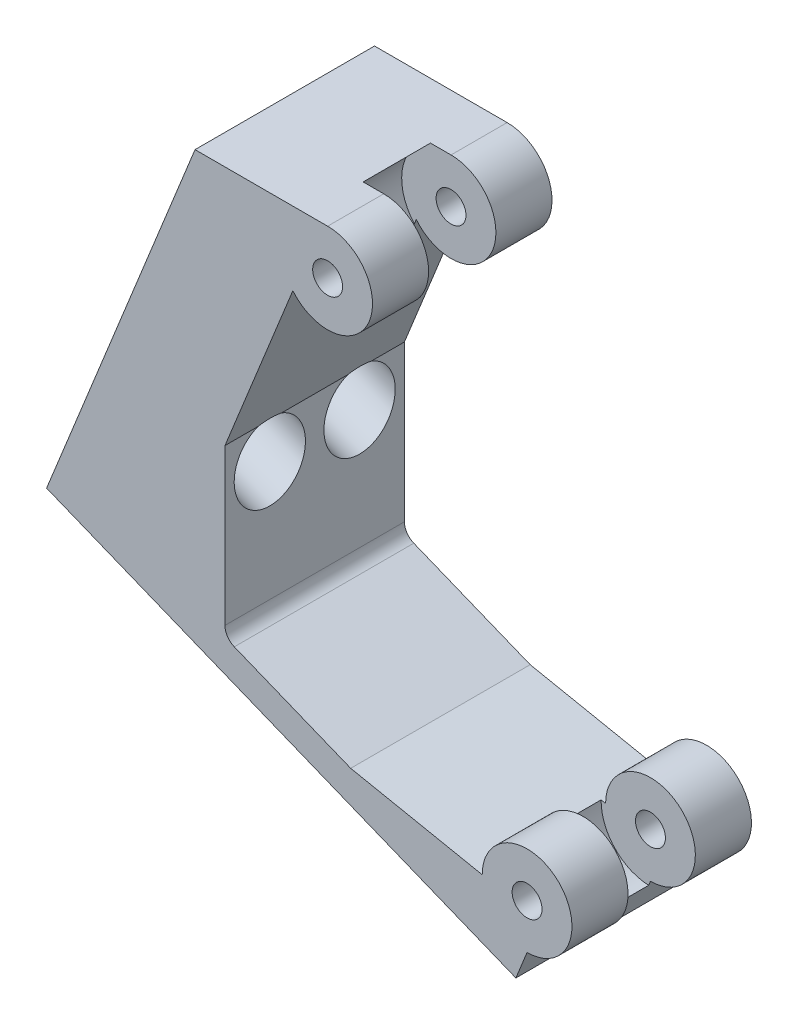
SolidWorks part; units mm, degrees
other "Markup1"
sketch "Sketch3" plane through (0, 0, 12) normal (0, 0, 1) x (1, 0, 0)
other "DetailItem1"
other "DetailItem3"
other "DetailItem5"
ref_plane "Front Plane" through (0, 0, 0) normal (0, 0, 1) x (1, 0, 0)
ref_plane "Top Plane" through (0, 0, 0) normal (0, 1, 0) x (1, 0, 0)
ref_plane "Right Plane" through (0, 0, 0) normal (1, 0, 0) x (0, 0, -1)
sketch "Sketch1" plane through (0, 0, 0) normal (0, 0, 1) x (1, 0, 0)
  line L2 (0, 6.6407) -> (0, 35.2105)
  line L3 (0, 35.2105) -> (8.8654, 35.2105)
  line L5 (6.5411, 30.3139) -> (2, 19.0743)
  line L6 (2, 19.0743) -> (2, 7.9897)
  line L7 (10.4069, 4.5931) -> (19.1992, 2.8287)
  line L11 (8.8654, 32.2105) -> (22.1992, 2.8287) construction
  line L15 (8.8654, 32.2105) -> (8.8654, 4.9405) construction
  line L16 (8.8654, 4.9405) -> (22.1992, 2.8287) construction
  line L17 (8.8654, 4.9405) -> (8.8654, -11.9834) construction
  line L21 (2, 7.9897) -> (10.4069, 4.5931)
  line L22 (-988.4786, -0.1713) -> (16.8603, -0.1713) construction
  line L23 (0, 6.6407) -> (21.45, -2.0257)
  line L24 (-905.7338, 372.5809) -> (46380.6427, -18732.3554) construction
  line L25 (22.1992, -0.1713) -> (50022.1992, -0.1713) construction
  line L26 (22.1992, -0.1713) -> (21.45, -2.0257)
  line L27 (-904.9846, 374.4353) -> (46381.392, -18730.501) construction
  line L28 (0.4221, 6.4701) -> (-46358.7706, 18736.7998) construction
  line L29 (2, 19.0743) -> (18732.3297, 46378.267) construction
  arc A0 (22.1992, -0.1713) -> (19.1992, 2.8287) centre (22.1992, 2.8287) ccw
  arc A1 (8.8654, 35.2105) -> (6.5411, 30.3139) centre (8.8654, 32.2105) cw
  circle A2 centre (8.8654, 32.2105) radius 1
  circle A3 centre (22.1992, 2.8287) radius 1
  dimension "D1" = 2
  dimension "D3" = 3
  dimension "D4" = 27.27
  dimension "D5" = 13.5
  dimension "D8" = 81
  dimension "D12" = 22
  dimension "D2" = 2
  dimension "D9" = 90
  dimension "D13" = 2
extrude "Boss-Extrude1" add sketch "Sketch1" along normal blind 12
ref_plane "midplane" through (0, 0, 6) normal (0, 0, 1) x (1, 0, 0)
sketch "Sketch2" plane through (0, 0, 6) normal (0, 0, 1) x (1, 0, 0)
  circle A0 centre (8.8654, 32.2105) radius 3.3
  circle A1 centre (22.1992, 2.8287) radius 3.3
  dimension "D1" = 6.6
extrude "Cut-Extrude1" cut sketch "Sketch2" against normal blind 2.25 and the other way blind 2.25
fillet "Fillet3" radius 1 1 edges at (2, 7.9897, 6)
ref_plane "Plane1" through (2.3065, 5.7088, 0) normal (-0.3746, -0.9272, 0) x (-0.9272, 0.3746, 0)
ref_plane "Plane2" through (-12.2296, 4.9411, 0) normal (-0.9272, 0.3746, 0) x (0, 0, -1)
sketch "Sketch4" plane through (-12.2296, 4.9411, 0) normal (-0.9272, 0.3746, 0) x (0, 0, -1)
  line L0 (6.6, -6.1571) -> (-6.6, -6.1571) construction
  line L1 (-12, -32.6466) -> (0, -32.6466)
  line L2 (-12, -32.6466) -> (-12, -6.1571)
  line L3 (-12, -6.1571) -> (0, -6.1571)
  line L4 (0, -32.6466) -> (0, -6.1571)
extrude "Boss-Extrude2" add sketch "Sketch4" against normal up to surface up to face at (0, 20.9256, 6)
sketch "Hole sketch" plane through (7.6836, 33.1417, 0) normal (-0.9272, 0.3746, 0) x (0, 0, -1)
  line L0 (-12, 17.4202) -> (0, 17.4202) construction
  line L1 (-8.25, 3.3877) -> (-3.75, 3.3877) construction
  line L2 (0, 24.8243) -> (0, 15.1722) construction
  line L3 (-6, -1.7766) -> (-6, 49998.2234) construction
  line L4 (-6, 52.9241) -> (-6, 14.2895) construction
  line L5 (-12, 19.6681) -> (-12, 15.1722) construction
  line L6 (-12, 3.4206) -> (-12, 10.3547) construction
  line L7 (-12, 6.8877) -> (-6, 6.8877) construction
  circle A0 centre (-9, 17.4202) radius 1.2884
  circle A1 centre (-3, 17.4202) radius 1.2884
  circle A2 centre (-6, 6.8877) radius 1.2884
  point P8 (-9, 17.4202)
  point P9 (-3, 17.4202)
  point P10 (-6, 6.8877)
  dimension "D2" = 2.5768
  dimension "D1" = 3
  dimension "D3" = 3.5
extrude "Screw shaft holes" cut sketch "Hole sketch" against normal through all both and the other way through all
sketch "Sketch5" plane through (-4.9057, 1.982, 0) normal (0.9272, -0.3746, 0) x (0, 0, -1)
  circle A0 centre (-6, 26.7191) radius 2.3813
  circle A1 centre (-9, 16.1866) radius 2.3813
  circle A2 centre (-3, 16.1866) radius 2.3813
  dimension "D1" = 4.7625
extrude "Screw counterbores" cut sketch "Sketch5" against normal blind 2.5918 and the other way blind 5
equation "\"axle-diameter\"=2"
equation "\"D1@Sketch1\"=\"axle-diameter\""
equation "\"switch-thickness\"=12"
equation "\"D1@Boss-Extrude1\"=\"switch-thickness\""
equation "\"base-width\"=4.0"
equation "\"axle-bushing-radius\"=3"
equation "\"D3@Sketch1\"= \"axle-bushing-radius\""
equation "\"D1@Sketch2\"=\"axle-bushing-radius\"*2.2"
equation "\"D1@Cut-Extrude1\"=\"switch-thickness\"/6+\"clearance\""
equation "\"D2@Cut-Extrude1\"=\"switch-thickness\"/6+\"clearance\""
equation "\"clearance\"= 0.25"
equation "\"arm-width\"=3.0"
equation "\"min-diameter\"=70"
